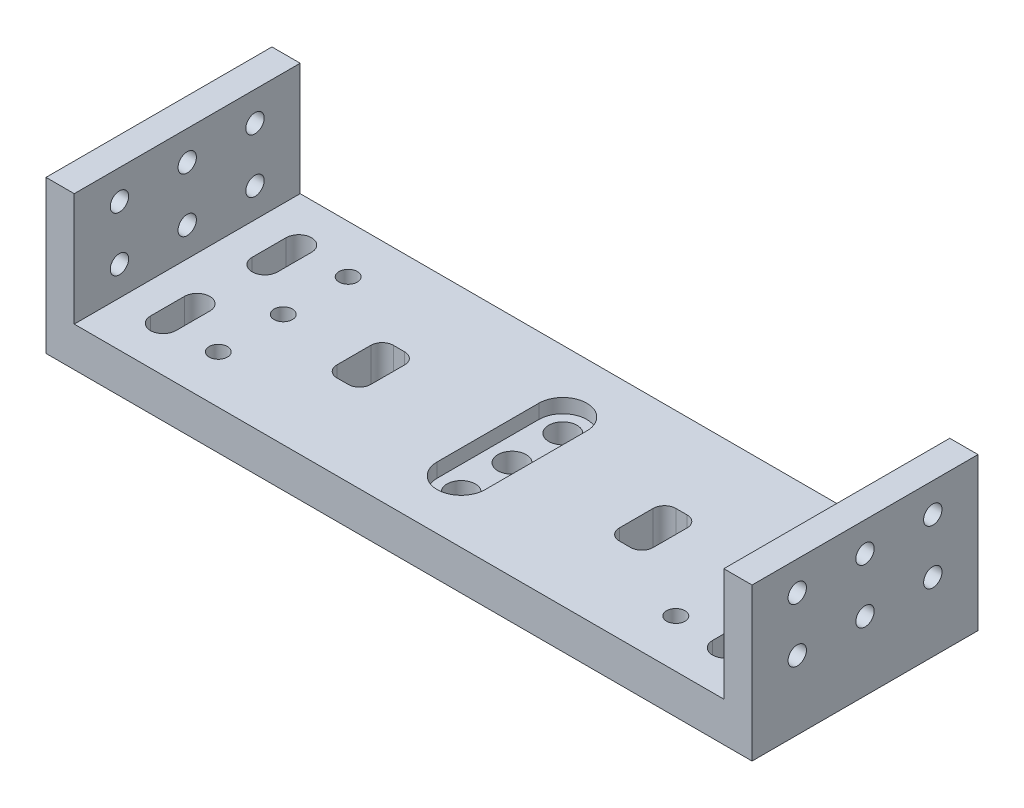
SolidWorks part; units mm, degrees
ref_plane "Plano frontal" through (0, 0, 0) normal (0, 0, 1) x (1, 0, 0)
ref_plane "Plano superior" through (0, 0, 0) normal (0, 1, 0) x (1, 0, 0)
ref_plane "Plano direito" through (0, 0, 0) normal (1, 0, 0) x (0, 0, -1)
sketch "Esboço1" plane through (0, 0, 0) normal (0, 1, 0) x (1, 0, 0)
  line L1 (62.5, -20) -> (-62.5, -20)
  line L2 (62.5, -20) -> (62.5, 20)
  line L3 (62.5, 20) -> (-62.5, 20)
  line L4 (-62.5, -20) -> (-62.5, 20)
  line L5 (62.5, -20) -> (-62.5, 20) construction
  line L6 (62.5, 20) -> (-62.5, -20) construction
  point P0 (0, 0)
  dimension "D1" = 125
  dimension "D2" = 40
extrude "base" add sketch "Esboço1" along normal blind 7
sketch "Esboço2" plane through (0, 7, 0) normal (0, 1, 0) x (1, 0, 0)
  line L0 (-62.5, -20) -> (62.5, -20) construction
  line L1 (62.5, 20) -> (57.5, 20)
  line L2 (62.5, 20) -> (62.5, -20)
  line L3 (62.5, -20) -> (57.5, -20)
  line L4 (57.5, 20) -> (57.5, -20)
  line L6 (-62.5, 20) -> (-57.5, 20)
  line L7 (-62.5, 20) -> (-62.5, -20)
  line L8 (-62.5, -20) -> (-57.5, -20)
  line L9 (-57.5, 20) -> (-57.5, -20)
  dimension "D1" = 5
extrude "suporte lateral" add sketch "Esboço2" along normal blind 20
sketch "Esboço3" plane through (0, 7, 0) normal (0, 1, 0) x (1, 0, 0)
  line L0 (0, 20) -> (0, -20) construction
  line L1 (57.5, 20) -> (-57.5, 20) construction
  line L2 (-57.5, -20) -> (57.5, -20) construction
  line L3 (-40.5, 20) -> (-40.5, -20) construction
  line L4 (0, 0) -> (-40.5, 0) construction
  line L5 (-40.5, 11.5) -> (0, 11.5) construction
  line L6 (-40.5, -11.5) -> (0, -11.5) construction
  line L8 (-20.25, 11.5) -> (-20.25, 0) construction
  line L9 (-20.25, 0) -> (-20.25, -11.5) construction
  circle A0 centre (-40.5, 0) radius 1.625
  circle A2 centre (-40.5, 11.5) radius 1.625
  circle A3 centre (-40.5, -11.5) radius 1.625
  circle A4 centre (40.5, 11.5) radius 1.625
  circle A5 centre (40.5, 0) radius 1.625
  circle A6 centre (40.5, -11.5) radius 1.625
  dimension "D2" = 3.25
  dimension "D1" = 40.5
  dimension "D3" = 11.5
extrude "furo motor" cut sketch "Esboço3" against normal up to surface (7 mm away) up to face at (0, 0, 0)
sketch "Esboço4" plane through (0, 7, 0) normal (0, 1, 0) x (1, 0, 0)
  line L0 (0, 20) -> (0, -20) construction
  line L1 (57.5, 20) -> (-57.5, 20) construction
  line L2 (-57.5, -20) -> (57.5, -20) construction
  line L3 (22, 5) -> (28, 5)
  line L4 (0, 0) -> (-25, 0) construction
  line L9 (28, -5) -> (28, 5)
  line L10 (22, -5) -> (28, -5)
  line L11 (-22, -5) -> (-28, -5)
  line L12 (-22, -5) -> (-22, 5)
  line L13 (-22, 5) -> (-28, 5)
  line L14 (-28, -5) -> (-28, 5)
  line L15 (-22, -5) -> (-28, 5) construction
  line L16 (-22, 5) -> (-28, -5) construction
  line L17 (22, -5) -> (22, 5)
  point P13 (-25, 0)
  dimension "D1" = 25
  dimension "D2" = 6
  dimension "D3" = 10
extrude "Corte-extrusão2" cut sketch "Esboço4" against normal through all
sketch "Esboço5" plane through (0, 7, 0) normal (0, 1, 0) x (1, 0, 0)
  line L0 (0, 20) -> (0, 9) construction
  line L3 (57.5, 20) -> (-57.5, 20) construction
  line L5 (0, -9) -> (0, -20) construction
  line L6 (-57.5, -20) -> (57.5, -20) construction
  circle A0 centre (0, 9) radius 2.5
  circle A1 centre (0, -9) radius 2.5
  dimension "D2" = 5
  dimension "D1" = 11
extrude "Corte-extrusão3" cut sketch "Esboço5" against normal through all both and the other way through all
sketch "Esboço7" plane through (0, 7, 0) normal (0, 1, 0) x (1, 0, 0)
  line L0 (-57.5, -20) -> (57.5, -20) construction
  line L1 (-57.5, 20) -> (-52, 20)
  line L2 (-57.5, 20) -> (-57.5, -20)
  line L3 (-57.5, -20) -> (-52, -20)
  line L4 (-52, 20) -> (-52, -20)
  line L5 (-40.5, 11.5) -> (-40.5, -20) construction
  line L6 (-47.5, 20) -> (-47.5, -20)
  line L7 (57.5, 20) -> (-57.5, 20) construction
  line L8 (-52, 20) -> (-47.5, 20) construction
  line L9 (-49.75, 20) -> (-49.75, -20) construction
  line L10 (-49.75, 12) -> (-49.75, 6) construction
  line L11 (-47.5, 12) -> (-47.5, 6)
  line L12 (-52, 12) -> (-52, 6)
  line L13 (-49.75, -12) -> (-49.75, -6) construction
  line L14 (-52, -12) -> (-52, -6)
  line L15 (-47.5, -12) -> (-47.5, -6)
  line L16 (0, 0) -> (-49.75, 0) construction
  line L17 (0, 20) -> (0, 0) construction
  line L18 (0, 0) -> (0, -20) construction
  line L19 (49.75, -12) -> (49.75, -6) construction
  line L20 (52, -12) -> (52, -6)
  line L21 (47.5, -12) -> (47.5, -6)
  line L22 (49.75, 12) -> (49.75, 6) construction
  line L23 (47.5, 12) -> (47.5, 6)
  line L24 (52, 12) -> (52, 6)
  arc A0 (-47.5, 12) -> (-52, 12) centre (-49.75, 12) ccw
  arc A1 (-52, 6) -> (-47.5, 6) centre (-49.75, 6) ccw
  arc A2 (-52, -12) -> (-47.5, -12) centre (-49.75, -12) ccw
  arc A3 (-47.5, -6) -> (-52, -6) centre (-49.75, -6) ccw
  arc A4 (52, -12) -> (47.5, -12) centre (49.75, -12) cw
  arc A5 (47.5, -6) -> (52, -6) centre (49.75, -6) cw
  arc A6 (47.5, 12) -> (52, 12) centre (49.75, 12) cw
  arc A7 (52, 6) -> (47.5, 6) centre (49.75, 6) cw
  point P16 (-49.75, 9)
  point P23 (-49.75, -9)
  point P37 (49.75, -9)
  point P44 (49.75, 9)
  dimension "D1" = 5.5
  dimension "D2" = 7
  dimension "D3" = 8
  dimension "D4" = 8
  dimension "D5" = 6
  dimension "D6" = 6
extrude "Corte-extrusão4" cut sketch "Esboço7" against normal through all contours A7 L24 A6 L23 | A5 L21 A4 L20 | L6 A3 L4 A2 | L4 A1 L6 A0 region at (-49.75, 7, -9) region at (-49.75, 7, 9) region at (49.75, 7, 9) region at (49.75, 7, -9)
sketch "Esboço8" plane through (0, 7, 0) normal (0, 1, 0) x (1, 0, 0)
  line L0 (0, 9) -> (0, -9) construction
  line L1 (4.25, 9) -> (4.25, -9)
  line L2 (-4.25, 9) -> (-4.25, -9)
  arc A0 (4.25, 9) -> (-4.25, 9) centre (0, 9) ccw
  arc A1 (-4.25, -9) -> (4.25, -9) centre (0, -9) ccw
  point P4 (0, 0)
  dimension "D1" = 4.25
extrude "Corte-extrusão5" cut sketch "Esboço8" against normal blind 2.5
sketch "Esboço9" plane through (0, 4.5, 0) normal (0, 1, 0) x (1, 0, 0)
  circle A0 centre (0, 0) radius 2.5
  dimension "D1" = 5
extrude "Corte-extrusão6" cut sketch "Esboço9" against normal through all contours A0
sketch "Esboço10" plane through (57.5, 0, 0) normal (-1, 0, 0) x (0, 0, 1)
  circle A0 centre (-12, 12.2) radius 1.6 construction
  circle A1 centre (-12, 21.8) radius 1.6 construction
  circle A2 centre (0, 21.8) radius 1.6 construction
  circle A3 centre (0, 12.2) radius 1.6 construction
  circle A4 centre (12, 12.2) radius 1.6 construction
  circle A5 centre (12, 21.8) radius 1.6 construction
  circle A6 centre (-12, 12.2) radius 1.6 construction
  circle A7 centre (-12, 21.8) radius 1.6 construction
  circle A8 centre (0, 21.8) radius 1.6 construction
  circle A9 centre (0, 12.2) radius 1.6 construction
  circle A10 centre (12, 12.2) radius 1.6 construction
  circle A11 centre (12, 21.8) radius 1.6 construction
  circle A12 centre (-12, 21.8) radius 1.625
  circle A13 centre (0, 21.8) radius 1.625
  circle A14 centre (12, 21.8) radius 1.625
  circle A15 centre (-12, 12.2) radius 1.625
  circle A16 centre (0, 12.2) radius 1.625
  circle A17 centre (12, 12.2) radius 1.625
  dimension "D1" = 3.25
extrude "Corte-extrusão7" cut sketch "Esboço10" against normal through all both and the other way through all
fillet "Filete1" radius 2 8 edges at (-22, 3.5, -5) (-28, 3.5, -5) (-22, 3.5, 5) (-28, 3.5, 5) (22, 3.5, -5) (22, 3.5, 5) (28, 3.5, -5) (28, 3.5, 5)
equation "\"3d\"= 0.25mm"
equation "\"D1@Esboço10\"=3.00mm + \"3d\""
equation "\"D2@Esboço3\"=3.00mm + \"3d\""
